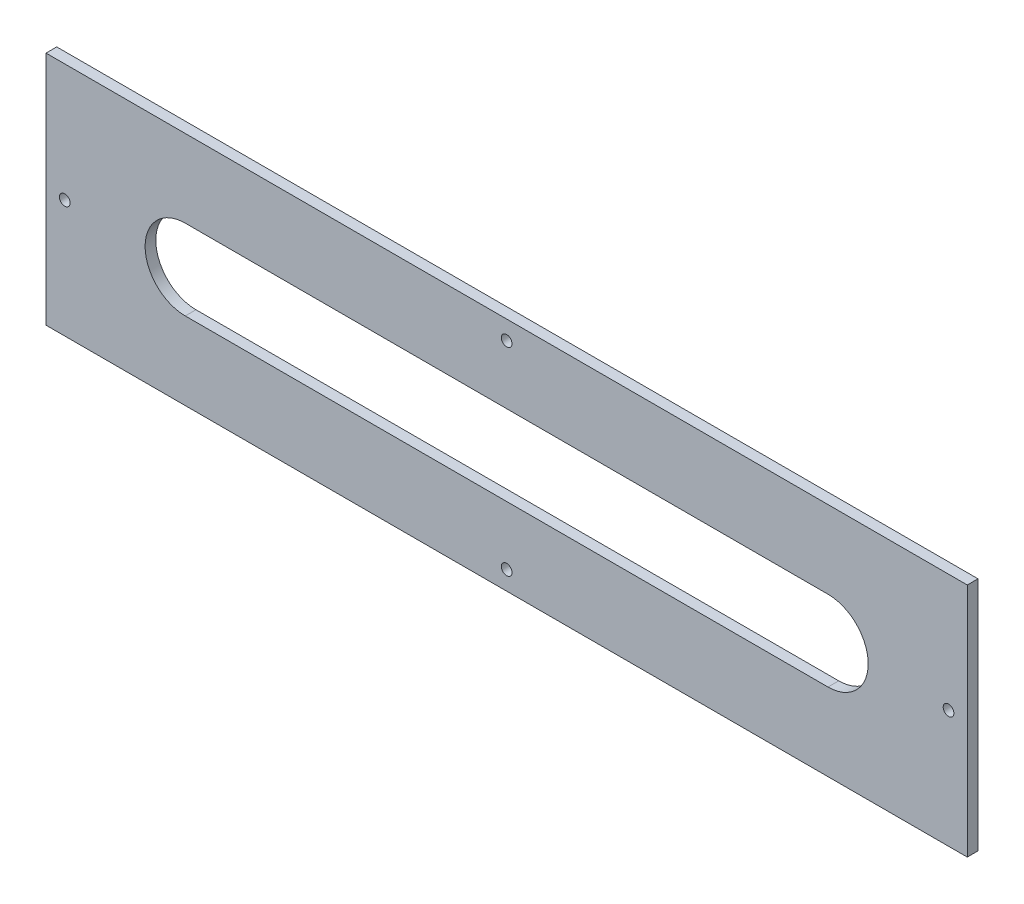
SolidWorks part; units mm, degrees
ref_plane "Piano frontale" through (0, 0, 0) normal (0, 0, 1) x (1, 0, 0)
ref_plane "Piano superiore" through (0, 0, 0) normal (0, 1, 0) x (1, 0, 0)
ref_plane "Piano destro" through (0, 0, 0) normal (1, 0, 0) x (0, 0, -1)
sketch "Schizzo1" plane through (0, 0, 0) normal (0, 0, 1) x (1, 0, 0)
  line L0 (-172, 351.6275) -> (-172, -66.2585) construction
  line L1 (0, 0) -> (-344, 0)
  line L2 (0, 0) -> (0, 88)
  line L3 (0, 88) -> (-344, 88)
  line L4 (-344, 0) -> (-344, 88)
  line L5 (-387.9788, 44) -> (120.8821, 44) construction
  line L6 (-292, 44) -> (-52, 44) construction
  line L7 (-292, 59) -> (-52, 59)
  line L8 (-292, 29) -> (-52, 29)
  arc A0 (-292, 59) -> (-292, 29) centre (-292, 44) ccw
  circle A1 centre (-7, 44) radius 2
  circle A2 centre (-172, 81) radius 2
  circle A3 centre (-337, 44) radius 2
  circle A4 centre (-172, 7) radius 2
  arc A5 (-52, 29) -> (-52, 59) centre (-52, 44) ccw
  point P9 (-172, 44)
  point P20 (-172, 44)
  dimension "D3" = 4
  dimension "D2" = 15
  dimension "D1" = 344
  dimension "314" = 88
  dimension "D4" = 7
  dimension "D5" = 240
  dimension "D6" = 7
extrude "Estrusione-Estrusione1" add sketch "Schizzo1" along normal blind 4
